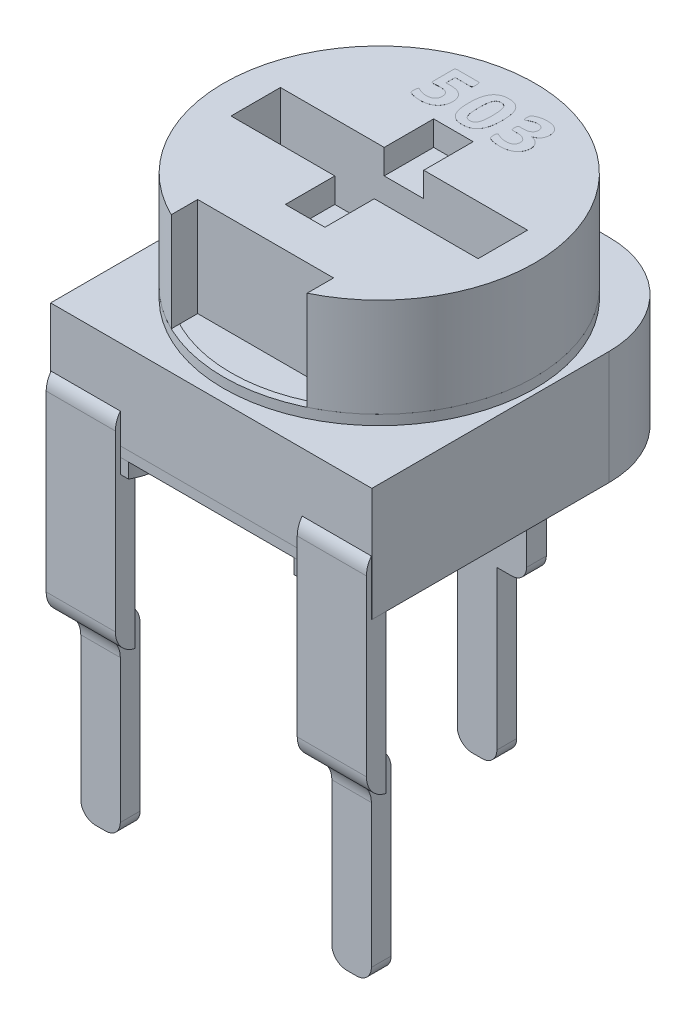
SolidWorks part; units mm, degrees
material "ABS"
ref_plane "Front Plane" through (0, 0, 0) normal (0, 0, 1) x (1, 0, 0)
ref_plane "Top Plane" through (0, 0, 0) normal (0, 1, 0) x (1, 0, 0)
ref_plane "Right Plane" through (0, 0, 0) normal (1, 0, 0) x (0, 0, -1)
sketch "Sketch1" plane through (0, 0, 0) normal (0, 1, 0) x (1, 0, 0)
  line L0 (0, 3.15) -> (0, -3.15) construction
  line L1 (0, 3.15) -> (0, 3.4) construction
  line L2 (0, -3.15) -> (0, -3.4) construction
  line L3 (-3.15, 0) -> (3.15, 0) construction
  line L4 (3.15, 0) -> (3.25, 0) construction
  line L5 (-3.15, 0) -> (-3.25, 0) construction
  line L6 (-3.25, -3.4) -> (3.25, -3.4)
  line L7 (-3.25, -3.4) -> (-3.25, 3.4)
  line L8 (-3.25, 3.4) -> (3.25, 3.4)
  line L9 (3.25, 3.4) -> (3.25, -3.4)
  circle A0 centre (0, 0) radius 3.15 construction
  dimension "D1" = 6.3
  dimension "D2" = 6.8
  dimension "D3" = 6.5
extrude "Boss-Extrude1" add sketch "Sketch1" along normal blind 2.3
sketch "Sketch2" plane through (0, 2.3, 0) normal (0, 1, 0) x (1, 0, 0)
  circle A0 centre (0, 0) radius 3.15 construction
  circle A1 centre (0, 0) radius 3.15
extrude "Boss-Extrude2" add sketch "Sketch2" along normal blind 0.2
fillet "Fillet1" radius 2 2 edges at (3.25, 1.15, -3.4) (-3.25, 1.15, -3.4)
sketch "Sketch3" plane through (0, 0, 0) normal (0, -1, 0) x (1, 0, 0)
  line L0 (0, 0) -> (0, -2.5) construction
  line L1 (-1.75, -2.5) -> (1.75, -2.5)
  line L6 (-2.25, -2) -> (-2.25, 2)
  line L7 (2.25, -2) -> (2.25, 2)
  line L8 (-2.25, 2) -> (-3, 2)
  line L9 (-3, 2) -> (-3, 3.4)
  line L10 (-3.25, 3.4) -> (3.25, 3.4) construction
  line L11 (2.25, 2) -> (3, 2)
  line L12 (3, 2) -> (3, 3.4)
  line L13 (3, 3.4) -> (-3, 3.4)
  line L14 (0, 0) -> (0, 3.4) construction
  arc A0 (-1.75, -2.5) -> (-2.25, -2) centre (-1.75, -2) cw
  arc A1 (1.75, -2.5) -> (2.25, -2) centre (1.75, -2) ccw
  point P20 (2.25, -2.5)
  dimension "D6" = 0.5
  dimension "D1" = 4.5
  dimension "D2" = 2.5
  dimension "D3" = 4.5
  dimension "D4" = 1.4
  dimension "D5" = 6
extrude "Cut-Extrude1" cut sketch "Sketch3" against normal blind 0.5
sketch "Sketch4" plane through (0, 0.5, 0) normal (0, -1, 0) x (1, 0, 0)
  line L8 (-3, 2) -> (-2.25, 2)
  line L9 (-2.25, 2) -> (-2.25, -2)
  line L10 (-1.75, -2.5) -> (1.75, -2.5)
  line L11 (2.25, -2) -> (2.25, 2)
  line L12 (2.25, 2) -> (3, 2)
  line L13 (3, 2) -> (3, 3.4)
  line L14 (3, 3.4) -> (-3, 3.4)
  line L15 (-3, 3.4) -> (-3, 2)
  line L16 (-3, 2) -> (-2.25, 2)
  line L17 (-2.25, 2) -> (-2.25, -2)
  line L18 (-1.75, -2.5) -> (1.75, -2.5)
  line L19 (2.25, -2) -> (2.25, 2)
  line L20 (2.25, 2) -> (3, 2)
  line L21 (3, 2) -> (3, 3.4)
  line L22 (3, 3.4) -> (-3, 3.4)
  line L23 (-3, 3.4) -> (-3, 2)
  arc A2 (-2.25, -2) -> (-1.75, -2.5) centre (-1.75, -2) ccw
  arc A3 (1.75, -2.5) -> (2.25, -2) centre (1.75, -2) ccw
  arc A4 (-2.25, -2) -> (-1.75, -2.5) centre (-1.75, -2) ccw
  arc A5 (1.75, -2.5) -> (2.25, -2) centre (1.75, -2) ccw
  dimension "D1" = 0
extrude "Boss-Extrude3" add sketch "Sketch4" along normal blind 0.2 separate body
sketch "Sketch5" plane through (0, 0.3, 0) normal (0, -1, 0) x (1, 0, 0)
  line L0 (0, 3.4) -> (0, 2.9) construction
  line L1 (3, 3.4) -> (-3, 3.4) construction
  line L2 (0, 2.9) -> (0, -2.18) construction
  line L3 (-2.54, 2.9) -> (2.54, 2.9) construction
  circle A0 centre (2.54, 2.9) radius 1
  circle A1 centre (-2.54, 2.9) radius 1
  circle A2 centre (0, -2.18) radius 1
  dimension "D2" = 5.08
  dimension "D4" = 2
  dimension "D1" = 0.5
  dimension "D3" = 5.08
extrude "Boss-Extrude4" add sketch "Sketch5" along normal up to surface (0.3 mm away) up to face at (0, 0, 0.1228)
sketch "Sketch6" plane through (0, 0.3, 0) normal (0, 1, 0) x (1, 0, 0)
  line L0 (-3.25, -3.4) -> (-3.25, -1)
  line L1 (-3.25, 1.4) -> (-3.25, -3.4) construction
  line L2 (-3.25, -1) -> (-4.35, -1)
  line L3 (-4.35, -1) -> (-4.35, -4.5)
  line L4 (-4.35, -4.5) -> (4.35, -4.5)
  line L5 (4.35, -4.5) -> (4.35, -1)
  line L6 (4.35, -1) -> (3.25, -1)
  line L7 (3.25, -3.4) -> (3.25, 1.4) construction
  line L8 (-3.25, -3.4) -> (3.25, -3.4)
  line L9 (3.25, -3.4) -> (3.25, -1)
  line L10 (0, 0) -> (0, -3.4) construction
  line L11 (0, -3.4) -> (0, -4.5) construction
  dimension "D1" = 3.5
extrude "Cut-Extrude2" cut sketch "Sketch6" against normal up to surface (0.3 mm away) up to face at (0, 0, -0.817)
sketch "Sketch8" plane through (0, 0.3, 0) normal (0, -1, 0) x (1, 0, 0)
  line L1 (-0.4, -1.98) -> (0.4, -1.98)
  line L2 (-0.4, -1.98) -> (-0.4, -2.38)
  line L3 (-0.4, -2.38) -> (0.4, -2.38)
  line L4 (0.4, -1.98) -> (0.4, -2.38)
  line L5 (-0.4, -1.98) -> (0.4, -2.38) construction
  line L6 (-0.4, -2.38) -> (0.4, -1.98) construction
  line L7 (-2.94, 3.1) -> (-2.14, 3.1)
  line L8 (-2.94, 3.1) -> (-2.94, 2.7)
  line L9 (-2.94, 2.7) -> (-2.14, 2.7)
  line L10 (-2.14, 3.1) -> (-2.14, 2.7)
  line L11 (-2.94, 3.1) -> (-2.14, 2.7) construction
  line L12 (-2.94, 2.7) -> (-2.14, 3.1) construction
  line L13 (2.94, 3.1) -> (2.14, 3.1)
  line L14 (2.94, 3.1) -> (2.94, 2.7)
  line L15 (2.94, 2.7) -> (2.14, 2.7)
  line L16 (2.14, 3.1) -> (2.14, 2.7)
  line L17 (2.94, 3.1) -> (2.14, 2.7) construction
  line L18 (2.94, 2.7) -> (2.14, 3.1) construction
  point P0 (0, -2.18)
  point P5 (-2.54, 2.9)
  point P11 (2.54, 2.9)
  dimension "D1" = 0.4
  dimension "D2" = 0.8
extrude "Boss-Extrude5" add sketch "Sketch8" along normal blind 7
sketch "Sketch9" plane through (0, 0.3, 0) normal (0, -1, 0) x (1, 0, 0)
  line L4 (0, -1.98) -> (0, -2.38) construction
  line L5 (0.4, -1.98) -> (-0.4, -1.98) construction
  line L6 (-0.4, -2.38) -> (0.4, -2.38) construction
  line L8 (-1, -1.98) -> (1, -1.98)
  line L9 (-1, -1.98) -> (-1, -2.38)
  line L10 (-1, -2.38) -> (1, -2.38)
  line L11 (1, -1.98) -> (1, -2.38)
  line L12 (-1, -1.98) -> (1, -2.38) construction
  line L13 (-1, -2.38) -> (1, -1.98) construction
  point P14 (0, -2.18)
  dimension "D1" = 2
extrude "Boss-Extrude6" add sketch "Sketch9" along normal blind 3.5
sketch "Sketch10" plane through (0, 0.3, 0) normal (0, -1, 0) x (1, 0, 0)
  line L0 (-2.54, 3.1) -> (-2.54, 3.5) construction
  line L1 (-2.14, 3.1) -> (-2.94, 3.1) construction
  line L2 (2.54, 3.1) -> (2.54, 3.5) construction
  line L3 (2.94, 3.1) -> (2.14, 3.1) construction
  line L4 (-2.94, 3.1) -> (-2.94, 2.7) construction
  line L5 (-3.24, 3.5) -> (-1.84, 3.5)
  line L6 (-3.24, 3.5) -> (-3.24, 3.1)
  line L7 (-3.24, 3.1) -> (-1.84, 3.1)
  line L8 (-1.84, 3.5) -> (-1.84, 3.1)
  line L10 (1.84, 3.5) -> (3.24, 3.5)
  line L11 (1.84, 3.5) -> (1.84, 3.1)
  line L12 (1.84, 3.1) -> (3.24, 3.1)
  line L13 (3.24, 3.5) -> (3.24, 3.1)
  dimension "D1" = 1.4
extrude "Boss-Extrude7" add sketch "Sketch10" along normal blind 3.5 and the other way blind 1
fillet "Fillet2" radius 0.5 2 edges at (2.54, 1.3, 3.5) (-2.54, 1.3, 3.5)
sketch "Sketch11" plane through (0, 0, 0) normal (1, 0, 0) x (0, 0, -1)
  line L0 (-3.4, 0) -> (1.4, 0) construction
  line L1 (-3.1, -2.8) -> (-2.7, -2.8)
  line L2 (-3.1, -2.8) -> (-3.1, 0)
  line L3 (-3.1, 0) -> (-2.7, 0)
  line L4 (-2.7, -2.8) -> (-2.7, 0)
  line L5 (-2.7, -6.7) -> (-2.7, 0.3) construction
  line L6 (-3.1, -2.8) -> (-3.1, -3.2) construction
extrude "Cut-Extrude3" cut sketch "Sketch11" against normal through all both and the other way through all
fillet "Fillet3" radius 0.5 4 edges at (-2.54, -2.8, 3.1) (2.54, -2.8, 3.1) (-2.54, -3.2, 3.5) (2.54, -3.2, 3.5)
fillet "Fillet4" radius 0.5 4 edges at (2.54, -2.8, 2.7) (-2.54, -2.8, 2.7) (2.54, -3.2, 3.1) (-2.54, -3.2, 3.1)
fillet "Fillet5" radius 0.3 12 edges at (-1, -3.2, -2.18) (1, -3.2, -2.18) (-0.4, -6.7, -2.18) (0.4, -6.7, -2.18) (2.14, -6.7, 2.9) (2.94, -6.7, 2.9) (-2.94, -6.7, 2.9) (-2.14, -6.7, 2.9) (-2.14, -2.7551, 3.1) (-2.94, -2.7551, 3.1) (2.14, -2.7551, 3.1) (2.94, -2.7551, 3.1)
sketch "Sketch12" plane through (0, 0.3, 0) normal (0, -1, 0) x (1, 0, 0)
  circle A0 centre (0, 0) radius 2
  circle A1 centre (0, 0) radius 1.5
  dimension "D1" = 4
  dimension "D2" = 3
extrude "Boss-Extrude8" add sketch "Sketch12" along normal blind 0.15
sketch "Sketch15" plane through (0, 2.5, 0) normal (0, 1, 0) x (1, 0, 0)
  circle A0 centre (0, 0) radius 3
  dimension "D1" = 6
extrude "Cut-Extrude4" cut sketch "Sketch15" against normal blind 0.5
sketch "Sketch14" plane through (0, 2.5, 0) normal (0, 1, 0) x (1, 0, 0)
  circle A1 centre (0, 0) radius 3.15
  circle A2 centre (0, 0) radius 3.15
  dimension "D1" = 0
extrude "Boss-Extrude9" add sketch "Sketch14" along normal blind 2 separate body
sketch "Set Angle of Knob" plane through (0, 4.5, 0) normal (0, 1, 0) x (1, 0, 0)
  line L0 (0, 0) -> (0, -3.15) construction
  line L1 (-2.5, 0) -> (2.5, 0) construction
  line L2 (-2.5, 0.5) -> (-2.5, -0.5)
  line L3 (2.5, 0.5) -> (2.5, -0.5)
  line L4 (-2.5, 0.5) -> (-0.4, 0.5)
  line L5 (-2.5, -0.5) -> (-0.4, -0.5)
  line L6 (0, 0) -> (0, -1.5) construction
  line L7 (0, 0) -> (0, 1.5) construction
  line L8 (0, 1.5) -> (0, 3.15) construction
  line L9 (0.4, 1.5) -> (-0.4, 1.5)
  line L10 (0.4, 1.5) -> (0.4, 0.5)
  line L11 (-0.4, 1.5) -> (-0.4, 0.5)
  line L12 (0.4, 0.5) -> (2.5, 0.5)
  line L13 (-0.4, -1.5) -> (0.4, -1.5)
  line L14 (-0.4, -1.5) -> (-0.4, -0.5)
  line L15 (0.4, -1.5) -> (0.4, -0.5)
  line L16 (0.4, -0.5) -> (2.5, -0.5)
  line L17 (0, -1.5) -> (0, -2.3) construction
  line L18 (-1.375, -2.3) -> (1.375, -2.3)
  line L19 (-1.375, -2.3) -> (-1.375, -3.8)
  line L20 (1.375, -2.3) -> (1.375, -3.8)
  line L21 (-1.375, -3.8) -> (1.375, -3.8)
  line L22 (-1, 0.25) -> (1, 0.25) construction
  line L23 (-1, 0.25) -> (-1, -0.25) construction
  line L24 (-1, -0.25) -> (1, -0.25) construction
  line L25 (1, -0.25) -> (1, 0.25) construction
  circle A0 centre (0, 0) radius 3.15 construction
  circle A1 centre (0, 0) radius 3.15 construction
  point P32 (0, 0.25)
  dimension "D1" = 1
  dimension "D2" = 0.8
  dimension "D3" = 1.5
  dimension "D4" = 5
  dimension "D5" = 90
  dimension "D6" = 2.75
  dimension "D7" = 1.5
  dimension "D8" = 1.8
  dimension "D9" = 0.25
  dimension "D10" = 0.25
  dimension "D11" = 2
extrude "TURN KNOB" cut sketch "Set Angle of Knob" against normal blind 2.3
sketch "Sketch17" plane through (0, 2, 0) normal (0, 1, 0) x (1, 0, 0)
  line L0 (-0.4, -1.5) -> (0.4, -1.5)
  line L1 (0.4, -1.5) -> (0.4, -0.5)
  line L2 (0.4, 1.5) -> (-0.4, 1.5)
  line L3 (-0.4, 1.5) -> (-0.4, 0.5)
  line L4 (-0.4, 0.5) -> (0.4, 0.5)
  line L5 (-0.4, -0.5) -> (0.4, -0.5)
  line L6 (-0.4, -0.5) -> (-0.4, -1.5)
  line L7 (0.4, 0.5) -> (0.4, 1.5)
extrude "Boss-Extrude10" add sketch "Sketch17" along normal blind 2
sketch "Sketch20" plane through (0, 2, 0) normal (0, 1, 0) x (1, 0, 0)
  line L0 (-1, 0.25) -> (1, 0.25) construction
  line L1 (-1, 0.25) -> (1, 0.25)
  line L2 (-1, -0.25) -> (1, -0.25) construction
  line L3 (-1, -0.25) -> (1, -0.25)
  line L4 (-1, 0.25) -> (-1, -0.25) construction
  line L5 (-1, 0.25) -> (-1, -0.25)
  line L6 (1, -0.25) -> (1, 0.25) construction
  line L7 (1, -0.25) -> (1, 0.25)
extrude "Cut-Extrude6" cut sketch "Sketch20" against normal blind 0.5
fillet "Fillet6" radius 0.2 2 edges at (1, 2, 0) (-1, 2, 0)
sketch "See Code in Properties" plane through (0, 4.5, 0) normal (0, 1, 0) x (1, 0, 0)
  line L0 (0, 1.5) -> (0, 1.7) construction
  line L1 (0.4, 1.5) -> (-0.4, 1.5) construction
  line L2 (0, 1.5) -> (0, 3.15) construction
  line L3 (-1.5, 1.7) -> (1.5, 1.7) construction
  text T0 "503" font "Calibri" height 0.9
  dimension "D1" = 0.2
  dimension "D2" = 3
extrude "Code Number" add sketch "See Code in Properties" along normal blind 0.001
